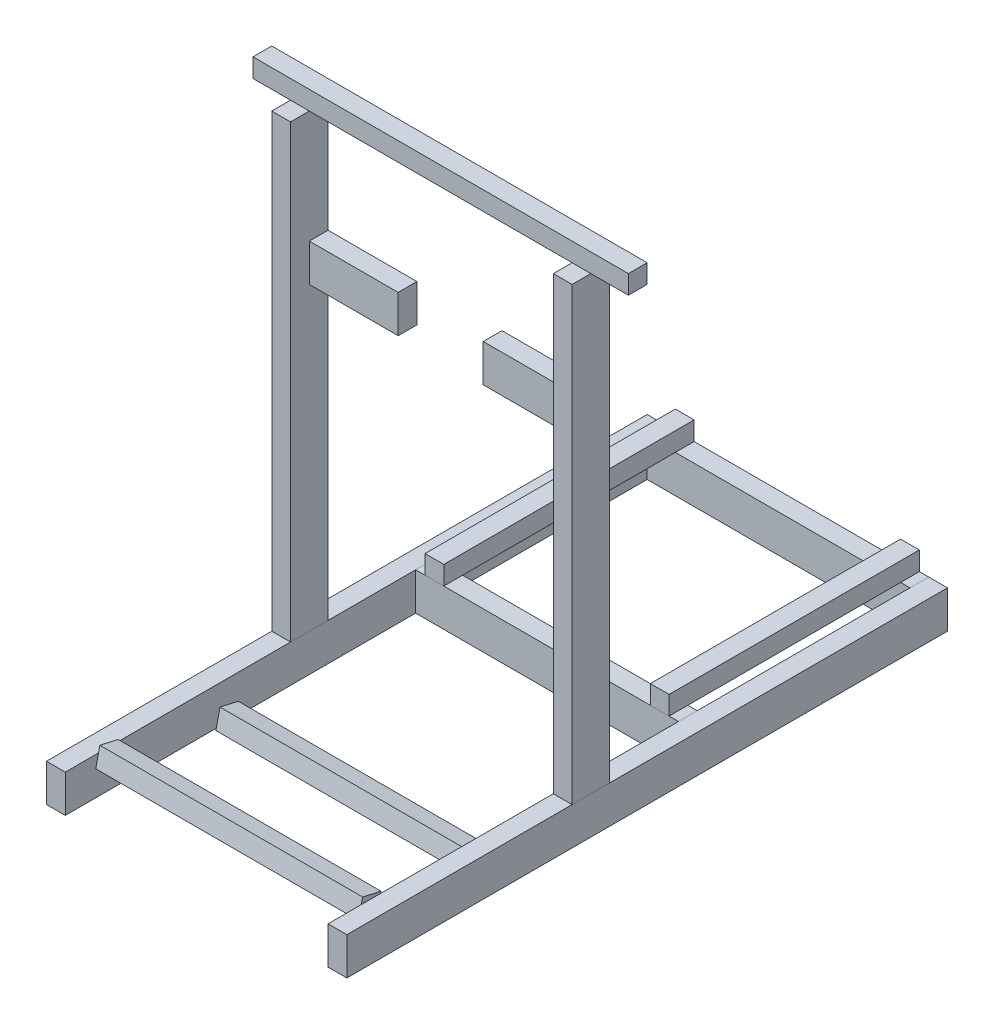
SolidWorks part; units mm, degrees
material "6061-T6 (SS)"
ref_plane "Front Plane" through (0, 0, 0) normal (0, 0, 1) x (1, 0, 0)
ref_plane "Top Plane" through (0, 0, 0) normal (0, 1, 0) x (1, 0, 0)
ref_plane "Right Plane" through (0, 0, 0) normal (1, 0, 0) x (0, 0, -1)
sketch "Sketch1" plane through (0, 0, 0) normal (0, 0, 1) x (1, 0, 0)
  line L0 (0, -90.2611) -> (0, 372.4246) construction
  line L1 (-266.7, 19.05) -> (-266.7, 95.25)
  line L2 (266.7, 19.05) -> (304.8, 19.05)
  line L3 (266.7, 19.05) -> (266.7, 95.25)
  line L4 (266.7, 95.25) -> (304.8, 95.25)
  line L5 (304.8, 19.05) -> (304.8, 95.25)
  line L6 (-266.7, 19.05) -> (-304.8, 19.05)
  line L7 (-304.8, 19.05) -> (-304.8, 95.25)
  line L8 (-266.7, 95.25) -> (-304.8, 95.25)
  dimension "D2" = 76.2
  dimension "D1" = 533.4
  dimension "D4" = 19.05
extrude "Boss-Extrude1" add sketch "Sketch1" against normal blind 1219.2
sketch "Sketch2" plane through (0, 0, 0) normal (1, 0, 0) x (0, 0, -1)
  line L0 (1219.2, 19.05) -> (0, 19.05) construction
  line L1 (1219.2, 95.25) -> (1181.1, 95.25)
  line L2 (1219.2, 95.25) -> (1219.2, 19.05)
  line L3 (1219.2, 19.05) -> (1181.1, 19.05)
  line L4 (1181.1, 95.25) -> (1181.1, 19.05)
  line L5 (749.3, 95.25) -> (711.2, 95.25)
  line L6 (749.3, 95.25) -> (749.3, 19.05)
  line L7 (749.3, 19.05) -> (711.2, 19.05)
  line L8 (711.2, 95.25) -> (711.2, 19.05)
  line L10 (0, 19.05) -> (0, 95.25) construction
  dimension "D1" = 38.1
  dimension "D2" = 76.2
  dimension "D4" = 38.1
  dimension "D3" = 76.2
  dimension "D5" = 508
  dimension "D6" = 711.2
extrude "Boss-Extrude2" add sketch "Sketch2" along normal up to next (266.7 mm away) and the other way up to next (266.7 mm away) separate body
sketch "Sketch3" plane through (0, 95.25, 0) normal (0, 1, 0) x (1, 0, 0)
  line L0 (0, -1000) -> (0, 49000) construction
  line L1 (-266.7, 457.2) -> (-266.7, 533.4)
  line L2 (266.7, 457.2) -> (304.8, 457.2)
  line L3 (266.7, 457.2) -> (266.7, 533.4)
  line L4 (266.7, 533.4) -> (304.8, 533.4)
  line L5 (304.8, 457.2) -> (304.8, 533.4)
  line L6 (-266.7, 457.2) -> (-304.8, 457.2)
  line L7 (-304.8, 457.2) -> (-304.8, 533.4)
  line L8 (-266.7, 533.4) -> (-304.8, 533.4)
  line L9 (266.7, 1219.2) -> (266.7, 0) construction
  line L10 (304.8, 0) -> (266.7, 0) construction
  dimension "D1" = 38.1
  dimension "D2" = 76.2
  dimension "D3" = 457.2
extrude "Boss-Extrude3" add sketch "Sketch3" along normal blind 914.4 separate body
sketch "Sketch4" plane through (0, 0, -711.2) normal (0, 0, 1) x (1, 0, 0)
  line L0 (0, -1002.4675) -> (0, 48997.5325) construction
  line L1 (-209.55, 133.35) -> (-209.55, 95.25)
  line L2 (209.55, 133.35) -> (247.65, 133.35)
  line L3 (209.55, 133.35) -> (209.55, 95.25)
  line L4 (209.55, 95.25) -> (247.65, 95.25)
  line L5 (247.65, 133.35) -> (247.65, 95.25)
  line L6 (-209.55, 133.35) -> (-247.65, 133.35)
  line L7 (-247.65, 133.35) -> (-247.65, 95.25)
  line L8 (-209.55, 95.25) -> (-247.65, 95.25)
  line L9 (-266.7, 95.25) -> (266.7, 95.25) construction
  point P13 (228.6, 133.35)
  point P14 (-228.6, 133.35)
  dimension "D1" = 38.1
  dimension "D3" = 457.2
  dimension "D2" = 38.1
extrude "Boss-Extrude4" add sketch "Sketch4" against normal blind 508 separate body
sketch "Sketch6" plane through (0, 0, 0) normal (1, 0, 0) x (0, 0, -1)
  line L0 (61.7895, 70.1417) -> (70.1417, 107.3149)
  line L25 (70.1417, 107.3149) -> (107.3149, 98.9627)
  line L26 (107.3149, 98.9627) -> (98.9627, 61.7895)
  line L27 (-609.6, 76.2) -> (-560.5375, 76.2) construction
  line L28 (98.9627, 61.7895) -> (61.7895, 70.1417)
  line L29 (-609.6, 38.1) -> (-553.7974, 38.1) construction
  line L30 (1219.2, 95.25) -> (0, 95.25) construction
  line L31 (1219.2, 19.05) -> (0, 19.05) construction
  line L32 (305.7085, 15.3373) -> (314.0607, 52.5105)
  line L33 (314.0607, 52.5105) -> (351.2339, 44.1583)
  line L34 (351.2339, 44.1583) -> (342.8817, 6.9851)
  line L35 (342.8817, 6.9851) -> (305.7085, 15.3373)
  line L36 (70.1417, 107.3149) -> (98.9627, 61.7895) construction
  line L37 (314.0607, 52.5105) -> (342.8817, 6.9851) construction
  line L38 (76.2, 47.3789) -> (92.9044, 121.7254) construction
  line L39 (47.3789, 92.9044) -> (121.7254, 76.2) construction
  line L40 (320.119, -7.4254) -> (336.8234, 66.9211) construction
  line L41 (291.2979, 38.1) -> (365.6444, 21.3956) construction
  line L42 (0, 19.05) -> (0, 95.25) construction
  point P13 (88.7283, 103.1388)
  point P14 (332.6473, 48.3344)
  point P21 (84.5522, 84.5522)
  point P22 (84.5522, 84.5522)
  point P23 (84.5522, 84.5522)
  point P24 (328.4712, 29.7478)
  point P25 (328.4712, 29.7478)
  point P26 (328.4712, 29.7478)
  dimension "D1" = 38.1
  dimension "D4" = 38.1
  dimension "D2" = 38.1
  dimension "D8" = 19.05
  dimension "D6" = 19.05
  dimension "D5" = 250
  dimension "D7" = 76.2
  dimension "D9" = 76.2
  dimension "D10" = 12.663
  dimension "D11" = 76.2
extrude "Boss-Extrude5" add sketch "Sketch6" along normal up to surface (266.7 mm away) and the other way up to surface (266.7 mm away) separate body up to face at (266.7, 57.15, -609.6) other way up to face at (-266.7, 57.15, -609.6)
sketch "Sketch7" plane through (0, 0, 0) normal (1, 0, 0) x (0, 0, -1)
  line L0 (533.4, 1009.65) -> (533.4, 95.25) construction
  line L1 (533.4, 781.05) -> (495.3, 781.05)
  line L2 (533.4, 781.05) -> (533.4, 704.85)
  line L3 (533.4, 704.85) -> (495.3, 704.85)
  line L4 (495.3, 781.05) -> (495.3, 704.85)
  line L5 (1219.2, 95.25) -> (0, 95.25) construction
  dimension "D1" = 38.1
  dimension "D2" = 76.2
  dimension "D3" = 609.6
extrude "Boss-Extrude6" add sketch "Sketch7" along normal up to next (266.7 mm away) and the other way up to next (266.7 mm away) separate body
extrude "Cut-Extrude1" cut sketch "Sketch7<2>" against normal mid plane 172.7
sketch "Sketch7<2>" plane through (0, 0, 0) normal (1, 0, 0) x (0, 0, -1) same geometry as "Sketch7"
sketch "Sketch8" plane through (0, 0, 0) normal (1, 0, 0) x (0, 0, -1)
  line L1 (495.3, 1047.75) -> (533.4, 1047.75)
  line L2 (495.3, 1047.75) -> (495.3, 1009.65)
  line L3 (495.3, 1009.65) -> (533.4, 1009.65)
  line L4 (533.4, 1047.75) -> (533.4, 1009.65)
  dimension "D1" = 38.1
  dimension "D2" = 38.1
extrude "Boss-Extrude7" add sketch "Sketch8" along normal mid plane 762 separate body
equation "\"W 1.5\"= 1.5"
equation "\"D1@Sketch2\"=\"W 1.5\""
equation "\"H 3\"= 3"
equation "\"D2@Sketch2\"=\"H 3\""
equation "\"D4@Sketch2\"=\"W 1.5\""
equation "\"D3@Sketch2\"=\"H 3\""
equation "\"D3@Sketch1\"=\"W 1.5\""
equation "\"D2@Sketch1\"=\"H 3\""
equation "\"D1@Sketch3\"=\"W 1.5\""
equation "\"D2@Sketch3\"=\"H 3\""
equation "\"H 1.5\"= 1.5"
equation "\"D1@Sketch4\"=\"W 1.5\""
equation "\"D2@Sketch4\"=\"H 1.5\""
equation "\"D1@Sketch6\"=\"W 1.5\""
equation "\"D2@Sketch6\"=\"W 1.5\""
equation "\"D3@Sketch6\"=\"H 1.5\""
equation "\"D4@Sketch6\"=\"H 1.5\""
equation "\"D1@Sketch7\"=\"W 1.5\""
equation "\"D2@Sketch7\"=\"H 3\""
equation "\"D1@Sketch8\"=\"W 1.5\""
equation "\"D2@Sketch8\"=\"H 1.5\""
